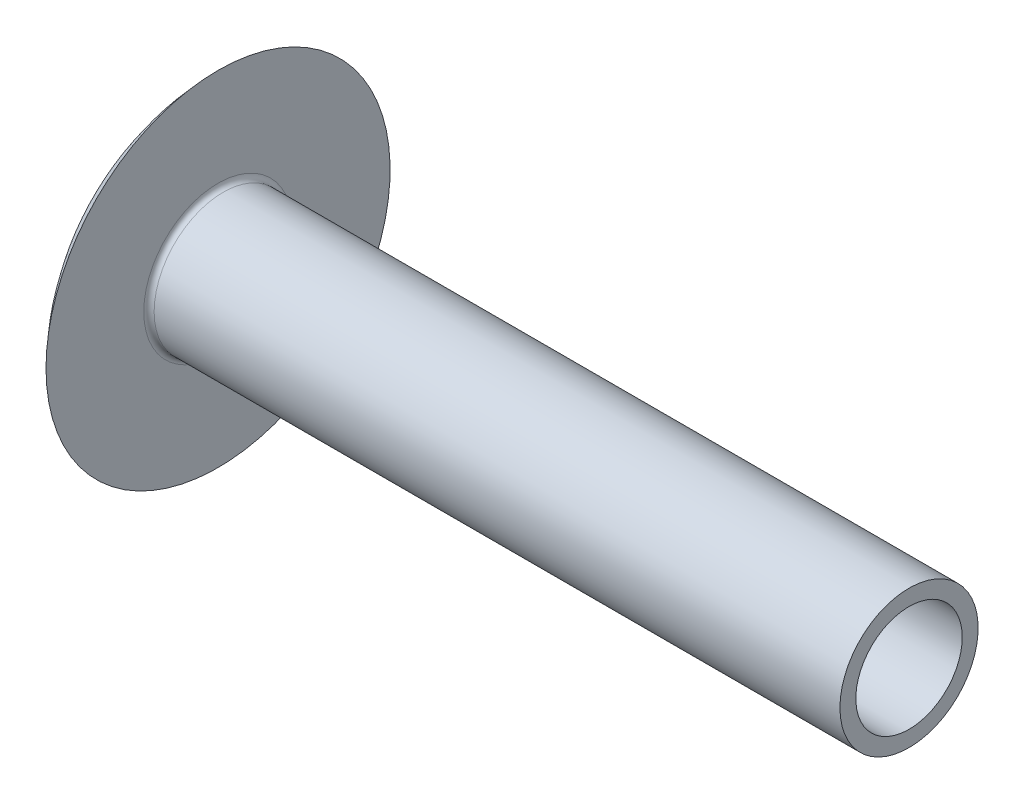
SolidWorks part; units mm, degrees
ref_plane "Front" through (0, 0, 0) normal (0, 0, 1) x (1, 0, 0)
ref_plane "Top" through (0, 0, 0) normal (0, 1, 0) x (1, 0, 0)
ref_plane "Right" through (0, 0, 0) normal (1, 0, 0) x (0, 0, -1)
sketch "Sketch1" plane through (0, 0, 0) normal (0, 0, 1) x (1, 0, 0)
  line L0 (-60.0944, 0) -> (17.9503, 0) construction
  line L1 (43.962, 0) -> (43.962, 4)
  line L2 (43.962, 4) -> (4.262, 4)
  line L3 (3.962, 4.3) -> (3.962, 9.96)
  line L4 (43.962, 0) -> (0, 0)
  arc A0 (3.962, 9.96) -> (0, 0) centre (14.5, 0) ccw
  arc A1 (4.262, 4) -> (3.962, 4.3) centre (4.262, 4.3) cw
  dimension "R" = 14.5
  dimension "r1" = 0.3
  dimension "d" = 8
  dimension "dk" = 19.92
  dimension "l" = 40
revolve "Base-Revolve" add sketch "Sketch1" angle 360 about L0
sketch "Sketch2" plane through (0, 0, 0) normal (0, 0, 1) x (1, 0, 0)
  line L0 (2.2377, 0) -> (-30.0312, 0) construction
  line L2 (43.962, 0) -> (43.962, 3.08)
  line L4 (43.962, 3.08) -> (36.312, 3.08)
  line L5 (36.312, 3.08) -> (34.0743, 0)
  line L6 (43.962, 0) -> (34.0743, 0)
  line L7 (43.962, -4) -> (43.962, 4) construction
  dimension "D1" = 54
  dimension "dt" = 6.16
  dimension "t" = 7.65
revolve "Cut-Revolve1" cut sketch "Sketch2" angle 360 about L0
